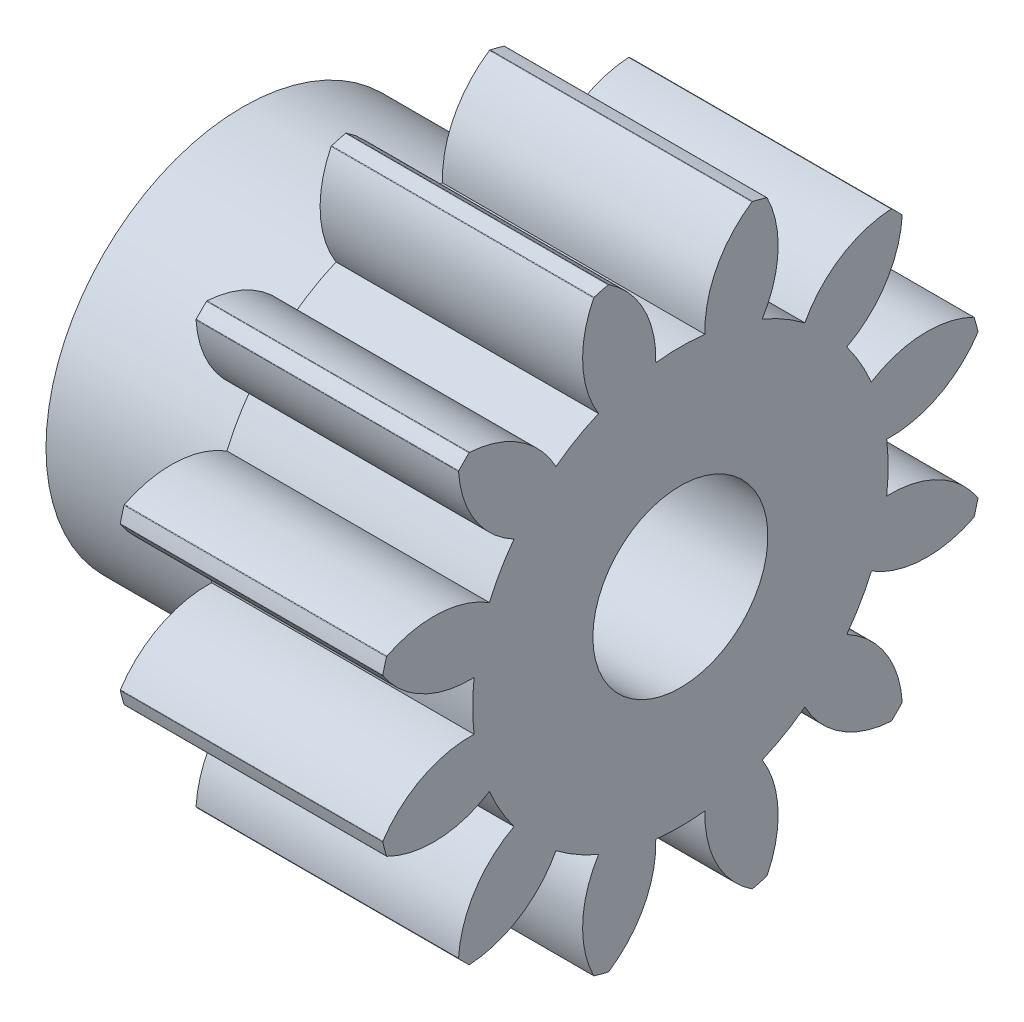
SolidWorks part; units mm, degrees
material "Nylon 101"
ref_plane "Plane1" through (0, 0, 0) normal (0, 0, 1) x (1, 0, 0)
ref_plane "Plane2" through (0, 0, 0) normal (0, 1, 0) x (1, 0, 0)
ref_plane "Plane3" through (0, 0, 0) normal (1, 0, 0) x (0, 0, -1)
sketch "HoldingSke" plane through (0, 0, 0) normal (0, 1, 0) x (1, 0, 0)
  line L0 (0, 0) -> (0.9781, -0.2079)
  line L1 (-15, 0) -> (100, 0) construction
  line L2 (0, 0) -> (-2.1039, 2.3779)
  line L3 (0, 0) -> (-11.863, 4.5341)
  line L4 (0, 0) -> (8.4473, 1.7955)
  line L5 (0, 0) -> (-46.8476, -17.4728)
  line L6 (0, 0) -> (-4.9738, -3.3558)
  line L7 (-2.1039, 2.3779) -> (8.6586, 51.2059)
  line L8 (-76.2, 54.61) -> (-75.5, 54.61)
  line L9 (-71.009, 38.7566) -> (-53.1078, 45.2721)
  line L10 (-76.2, 71.12) -> (104.1128, 71.12)
  line L11 (0, 0) -> (-6, 0)
  line L12 (-76.2, 101.6) -> (-76.162, 101.6)
  line L13 (24.9733, 27.94) -> (52.9518, 28.4284)
  line L14 (24.9733, 27.94) -> (24.9743, 27.94)
  line L15 (24.9733, 27.94) -> (100.4006, 29.5858)
  line L16 (-63.627, -1) -> (-12.827, -1)
  circle A0 centre (0, 0) radius 2
  circle A1 centre (0, 0) radius 4.749
  circle A2 centre (0, 0) radius 37.5
  circle A3 centre (0, 0) radius 2
  dimension "Num_teeth" = 12
  dimension "Pitch_radius" = 180.3128
  dimension "Width" = 6
  dimension "Thickness" = 6
sketch "BasProSke" plane through (0, 0, 0) normal (0, 1, 0) x (1, 0, 0)
  line L0 (-10, 0) -> (60, 0) construction
  line L1 (0, 0) -> (0, 7)
  line L2 (0, 0) -> (6, 0)
  line L3 (6, 0) -> (6, 7)
  line L4 (6, 7) -> (0, 7)
  dimension "Thickness" = 6
  dimension "Diameter" = 14
revolve "Base-Revolve" add sketch "BasProSke" angle 360 about L0
sketch "TooCutSke" plane through (0, 0, 0) normal (1, 0, 0) x (0, 0, -1)
  line L1 (0, 0) -> (0, 107) construction
  line L2 (0, 0) -> (-0.8496, 5.9395) construction
  line L3 (0, 0) -> (-3.0836, 11.5081) construction
  line L4 (-0.8496, 5.9395) -> (-1.5418, 5.7541) construction
  arc A0 (0.5622, 4.7156) -> (-0.5622, 4.7156) centre (0, 0) ccw
  arc A1 (1.6729, 6.8233) -> (-1.6729, 6.8233) centre (0, 0) ccw
  circle A2 centre (0, 0) radius 6 construction
  circle A3 centre (0, 0) radius 5.6382 construction
  arc A4 (-0.5622, 4.7156) -> (-1.6729, 6.8233) centre (-2.9608, 4.7982) ccw
  arc A5 (1.6729, 6.8233) -> (0.5622, 4.7156) centre (2.9608, 4.7982) ccw
extrude "ToothCut" cut sketch "TooCutSke" along normal through all
fillet "Breaks" radius 0.02 2 edges at (3, 6.8043, -1.6435) (3, 6.8043, 1.6435) tangent propagation no
fillet "RootFillets" [suppressed] radius 0.251
pattern_circular "TeethCuts" count 12 over 360 about axis through (-10, 0, 0) along (1, 0, 0) of "ToothCut", "Breaks", "RootFillets"
sketch "HubNeaOneSke" plane through (0, 0, 0) normal (-1, 0, 0) x (0, 0, 1)
  circle A0 centre (0, 0) radius 4.749
  dimension "Diameter" = 9.498
extrude "HubNearOne" [suppressed] add sketch "HubNeaOneSke" along normal blind 44.0001
sketch "HubNeaBotSke" plane through (0, 0, 0) normal (-1, 0, 0) x (0, 0, 1)
  circle A0 centre (0, 0) radius 4.749
  dimension "Diameter" = 9.498
extrude "HubNearBoth" [suppressed] add sketch "HubNeaBotSke" along normal blind 22
ref_plane "FarPln" through (6, 0, 0) normal (1, 0, 0) x (0, 0, -1)
sketch "HubFarSke" plane through (6, 0, 0) normal (1, 0, 0) x (0, 0, -1)
  circle A0 centre (0, 0) radius 4.749
  dimension "Diameter" = 9.498
extrude "HubFar" [suppressed] add sketch "HubFarSke" along normal blind 22
sketch "BorSke" plane through (0, 0, 0) normal (1, 0, 0) x (0, 0, -1)
  circle A0 centre (0, 0) radius 2
  dimension "Diameter" = 4
extrude "Bore" cut sketch "BorSke" along normal mid plane 100.0001
sketch "KeySke" plane through (0, 0, 0) normal (1, 0, 0) x (0, 0, -1)
  line L0 (-0.8, 0) -> (-0.8, 2.7)
  line L1 (-0.8, 2.7) -> (0.8, 2.7)
  line L2 (0.8, 2.7) -> (0.8, 0)
  line L3 (0, 0) -> (0, 34) construction
  line L4 (-0.8, 0) -> (0.8, 0)
  dimension "Width" = 1.6
extrude "Keyway" [suppressed] cut sketch "KeySke" along normal mid plane 100.0001
pattern_circular "Keyway2" [suppressed] count 2 every 90 about axis through (-10, 0, 0) along (1, 0, 0) reverse direction yes
ref_plane "Плоскость1" through (-4, 0, 0) normal (-1, 0, 0) x (0, 0, 1)
sketch "Эскиз3" plane through (-4, 0, 0) normal (-1, 0, 0) x (0, 0, 1)
  line L0 (0, 0) -> (-0.9356, 2.3183) construction
  line L1 (-0.7859, 1.9474) -> (-0.723, 2.3932)
  line L2 (-0.7859, 1.9474) -> (-1.1405, 2.2247)
  line L3 (-0.1456, 2.0949) -> (0.0519, 2.4995)
  line L4 (-0.1456, 2.0949) -> (-0.3972, 2.4682)
  line L5 (0, 0) -> (-0.1734, 2.494) construction
  line L6 (0.5089, 2.0374) -> (0.8217, 2.3611)
  line L7 (0.5089, 2.0374) -> (0.385, 2.4702)
  line L8 (0, 0) -> (0.6058, 2.4255) construction
  line L9 (1.1136, 1.7804) -> (1.5111, 1.9916)
  line L10 (1.1136, 1.7804) -> (1.1295, 2.2303)
  line L11 (0, 0) -> (1.3257, 2.1196) construction
  line L12 (1.6093, 1.3492) -> (2.0526, 1.4272)
  line L13 (1.6093, 1.3492) -> (1.7634, 1.7721)
  line L14 (0, 0) -> (1.9158, 1.6062) construction
  line L15 (1.9474, 0.7859) -> (2.3932, 0.723)
  line L16 (1.9474, 0.7859) -> (2.2247, 1.1405)
  line L17 (0, 0) -> (2.3183, 0.9356) construction
  line L18 (2.0949, 0.1456) -> (2.4995, -0.0519)
  line L19 (2.0949, 0.1456) -> (2.4682, 0.3972)
  line L20 (0, 0) -> (2.494, 0.1734) construction
  line L21 (2.0374, -0.5089) -> (2.3611, -0.8217)
  line L22 (2.0374, -0.5089) -> (2.4702, -0.385)
  line L23 (0, 0) -> (2.4255, -0.6058) construction
  line L24 (1.7804, -1.1136) -> (1.9916, -1.5111)
  line L25 (1.7804, -1.1136) -> (2.2303, -1.1295)
  line L26 (0, 0) -> (2.1196, -1.3257) construction
  line L27 (1.3492, -1.6093) -> (1.4272, -2.0526)
  line L28 (1.3492, -1.6093) -> (1.7721, -1.7634)
  line L29 (0, 0) -> (1.6062, -1.9158) construction
  line L30 (0.7859, -1.9474) -> (0.723, -2.3932)
  line L31 (0.7859, -1.9474) -> (1.1405, -2.2247)
  line L32 (0, 0) -> (0.9356, -2.3183) construction
  line L33 (0.1456, -2.0949) -> (-0.0519, -2.4995)
  line L34 (0.1456, -2.0949) -> (0.3972, -2.4682)
  line L35 (0, 0) -> (0.1734, -2.494) construction
  line L36 (-0.5089, -2.0374) -> (-0.8217, -2.3611)
  line L37 (-0.5089, -2.0374) -> (-0.385, -2.4702)
  line L38 (0, 0) -> (-0.6058, -2.4255) construction
  line L39 (-1.1136, -1.7804) -> (-1.5111, -1.9916)
  line L40 (-1.1136, -1.7804) -> (-1.1295, -2.2303)
  line L41 (0, 0) -> (-1.3257, -2.1196) construction
  line L42 (-1.6093, -1.3492) -> (-2.0526, -1.4272)
  line L43 (-1.6093, -1.3492) -> (-1.7634, -1.7721)
  line L44 (0, 0) -> (-1.9158, -1.6062) construction
  line L45 (-1.9474, -0.7859) -> (-2.3932, -0.723)
  line L46 (-1.9474, -0.7859) -> (-2.2247, -1.1405)
  line L47 (0, 0) -> (-2.3183, -0.9356) construction
  line L48 (-2.0949, -0.1456) -> (-2.4995, 0.0519)
  line L49 (-2.0949, -0.1456) -> (-2.4682, -0.3972)
  line L50 (0, 0) -> (-2.494, -0.1734) construction
  line L51 (-2.0374, 0.5089) -> (-2.3611, 0.8217)
  line L52 (-2.0374, 0.5089) -> (-2.4702, 0.385)
  line L53 (0, 0) -> (-2.4255, 0.6058) construction
  line L54 (-1.7804, 1.1136) -> (-1.9916, 1.5111)
  line L55 (-1.7804, 1.1136) -> (-2.2303, 1.1295)
  line L56 (0, 0) -> (-2.1196, 1.3257) construction
  line L57 (-1.3492, 1.6093) -> (-1.4272, 2.0526)
  line L58 (-1.3492, 1.6093) -> (-1.7721, 1.7634)
  line L59 (0, 0) -> (-1.6062, 1.9158) construction
  circle A0 centre (0, 0) radius 2.5
  circle A1 centre (0, 0) radius 2.1
  circle A2 centre (0, 0) radius 4.5
  circle A3 centre (0, 0) radius 2.2
  point P87 (0, 0)
  dimension "D1" = 5
  dimension "D2" = 4.2
  dimension "D4" = 9
  dimension "D6" = 4.4
  dimension "D3" = 30
  dimension "D5" = 20
extrude "Бобышка-Вытянуть2" add sketch "Эскиз3" against normal blind 4 separate body contours L1 A0 L2 | L3 A0 L4 | L6 A0 L7 | L9 A0 L10 | L12 A0 L13 | L15 A0 L16 | L18 A0 L19 | L57 A0 L58 | L54 A0 L55 | L51 A0 L52 | L48 A0 L49 | L45 A0 L46 | L42 A0 L43 | L39 A0 L40 | L36 A0 L37 | L21 A0 L22 | L24 A0 L25 | L27 A0 L28 | L30 A0 L31 | L33 A0 L34 | A2 A0 region at (-4, 2.205, -0.8898) region at (-4, 2.372, -0.1649) region at (-4, 1.8221, -1.5276) region at (-4, 2.3069, 0.5762) region at (-4, 1.2609, -2.0159) region at (-4, 2.0159, 1.2609) region at (-4, 0.5762, -2.3069) region at (-4, 1.5276, 1.8221) region at (-4, -0.1649, -2.372) region at (-4, 0.8898, 2.205) region at (-4, -0.8898, -2.205) region at (-4, 0.1649, 2.372) region at (-4, -1.5276, -1.8221) region at (-4, -2.0159, -1.2609) region at (-4, -0.5762, 2.3069) region at (-4, -2.3069, -0.5762) region at (-4, -1.2609, 2.0159) region at (-4, -2.372, 0.1649) region at (-4, -1.8221, 1.5276) region at (-4, -2.205, 0.8898) region at (-4, 0, -4.3727)
sketch "Эскиз4" plane through (6, 0, 0) normal (1, 0, 0) x (0, 0, -1)
  circle A0 centre (0, 0) radius 2
equation "' \"Module@HoldingSke\" = 6.35"
equation "' \"Num_teeth@HoldingSke\" = 12"
equation "' \"Ap@HoldingSke\" =  20"
equation "' \"Ap@HoldingSke\" = 20"
equation "' \"Width@HoldingSke\" = 0.5 * 25.4"
equation "' \"Hub_dia@HoldingSke\"= 1 * 25.4"
equation "' \"Hub_dia@HoldingSke\" = 1 * 25.4"
equation "' \"Overall_len@HoldingSke\" = 1.0 * 25.4"
equation "' \"Bore@HoldingSke\" = 0.75 * 25.4"
equation "' \"T_dim@HoldingSke\" = 0.1 * 25.4"
equation "' \"Width@KeySke\" = 0.25 * 25.4"
equation "' \"Show_teeth@HoldingSke\" = 13"
equation "' \"Backlash@HoldingSke\" = 0.009 * 25.4"
equation "' \"Addendum_fac@HoldingSke\" = 1.0"
equation "' \"Dedendum_fac@HoldingSke\" = 1.25"
equation "' \"Dedendum_add@HoldingSke\" = 0.00005 * 25.4"
equation "' \"Clearance_fac@HoldingSke\" = 0.25"
equation "\"Pitch@HoldingSke\" = 1 / \"Module@HoldingSke\""
equation "\"Overcut_dia@TooCutSke\" = (\"Num_teeth@HoldingSke\" + 2 * \"Addendum_fac@HoldingSke\") / \"Pitch@HoldingSke\" + 0.002 * 25.4"
equation "\"Pitch_dia@TooCutSke\" = \"Num_teeth@HoldingSke\" / \"Pitch@HoldingSke\""
equation "\"Base_dia@TooCutSke\" = \"Num_teeth@HoldingSke\" / \"Pitch@HoldingSke\" * cos((\"Ap@HoldingSke\"  * 3.14159265 / 180))"
equation "\"Root_dia@TooCutSke\" = (\"Num_teeth@HoldingSke\" + 2) / \"Pitch@HoldingSke\" - 2 * (\"Addendum_fac@HoldingSke\" + \"Dedendum_fac@HoldingSke\") / \"Pitch@HoldingSke\" - \"Dedendum_add@HoldingSke\" * 2"
equation "\"Half_ang@TooCutSke\" = 180 / \"Num_teeth@HoldingSke\""
equation "\"Half_CT@TooCutSke\" = \"Num_teeth@HoldingSke\" / \"Pitch@HoldingSke\" * sin((3.14159265 / 2 / \"Num_teeth@HoldingSke\")) / 2 - 7 * \"Backlash@HoldingSke\" / 4"
equation "\"Flank_rad@TooCutSke\" = \"Num_teeth@HoldingSke\" / \"Pitch@HoldingSke\" / 5"
equation "\"Radius@RootFillets\" = \"Clearance_fac@HoldingSke\" / \"Pitch@HoldingSke\" + \"Dedendum_add@HoldingSke\""
equation "\"Break_rad@Breaks\" = 0.02 / \"Pitch@HoldingSke\""
equation "\"Thickness@HoldingSke\" = \"Width@HoldingSke\""
equation "\"OAL@HoldingSke\" = \"Thickness@HoldingSke\""
equation "\"MHD@HoldingSke\" = (\"Num_teeth@HoldingSke\" + 2) / \"Pitch@HoldingSke\" - 2 * (\"Addendum_fac@HoldingSke\" + \"Dedendum_fac@HoldingSke\")  / \"Pitch@HoldingSke\" - \"Dedendum_add@HoldingSke\" * 2"
equation "\"MBD@HoldingSke\" = (\"Num_teeth@HoldingSke\" + 2) / \"Pitch@HoldingSke\" - 2 * (\"Addendum_fac@HoldingSke\" + \"Dedendum_fac@HoldingSke\")  / \"Pitch@HoldingSke\" - \"Dedendum_add@HoldingSke\" * 2 - 0.002 * 25.4"
equation "\"MHD@HoldingSke\" = ((sgn( \"MHD@HoldingSke\" - \"Hub_dia@HoldingSke\" )-1)*( \"MHD@HoldingSke\" - \"Hub_dia@HoldingSke\" ))/-2+ \"Hub_dia@HoldingSke\""
equation "\"MBD@HoldingSke\" = ((sgn( \"MBD@HoldingSke\" - \"Bore@HoldingSke\" )-1)*( \"MBD@HoldingSke\" - \"Bore@HoldingSke\" ))/-2+ \"Bore@HoldingSke\""
equation "\"OAL@HoldingSke\" = ((sgn( \"OAL@HoldingSke\" - \"Overall_len@HoldingSke\" )+1)*( \"OAL@HoldingSke\" - \"Overall_len@HoldingSke\" ))/2 + \"Overall_len@HoldingSke\" + 0.000002 * 25.4"
equation "\"Num_teeth@TeethCuts\" = int( \"Show_teeth@HoldingSke\" ) + 1"
equation "\"Num_teeth@TeethCuts\" = ((sgn( \"Num_teeth@TeethCuts\" - \"Num_teeth@HoldingSke\" )-1)*( \"Num_teeth@TeethCuts\" - \"Num_teeth@HoldingSke\" ))/-2+ \"Num_teeth@HoldingSke\""
equation "\"Num_teeth@TeethCuts\" = ((sgn( \"Num_teeth@TeethCuts\" - 2.0)+1)*( \"Num_teeth@TeethCuts\" - 2.0))/2 +2.0"
equation "\"Angle@TeethCuts\" = 360.0 / \"Num_teeth@HoldingSke\""
equation "\"Diameter@BasProSke\" = (\"Num_teeth@HoldingSke\" + 2 * \"Addendum_fac@HoldingSke\") / \"Pitch@HoldingSke\""
equation "\"Thickness@BasProSke\"  = \"Thickness@HoldingSke\""
equation "' \"Fillet_rad@BasProSke\" =  \"Thickness@HoldingSke\" * 0.05"
equation "' \"Fillet_rad@BasProSke\" = \"Thickness@HoldingSke\" * 0.05"
equation "\"MHD@HoldingSke\" = ((sgn( \"MHD@HoldingSke\" - \"Root_dia@TooCutSke\" )-1)*( \"MHD@HoldingSke\" - \"Root_dia@TooCutSke\" ))/-2+ \"Root_dia@TooCutSke\""
equation "\"Diameter@HubNeaOneSke\" = \"MHD@HoldingSke\""
equation "\"Length@HubNearOne\" = \"OAL@HoldingSke\" - \"Thickness@BasProSke\""
equation "\"Diameter@HubNeaBotSke\" = \"MHD@HoldingSke\""
equation "\"Length@HubNearBoth\" = ( \"OAL@HoldingSke\" - \"Thickness@BasProSke\" ) / 2.0"
equation "\"Thickness@FarPln\" = \"Thickness@BasProSke\""
equation "\"Diameter@HubFarSke\" = \"MHD@HoldingSke\""
equation "\"Length@HubFar\" = ( \"OAL@HoldingSke\" - \"Thickness@BasProSke\" ) / 2.0"
equation "\"Diameter@BorSke\" = \"MBD@HoldingSke\""
equation "\"D1@Bore\" = \"OAL@HoldingSke\" * 2.0"
equation "\"D1@Keyway\" = \"OAL@HoldingSke\" * 2.0"
equation "\"Offset@KeySke\" = \"T_dim@HoldingSke\" + \"MBD@HoldingSke\" / 2.0"
